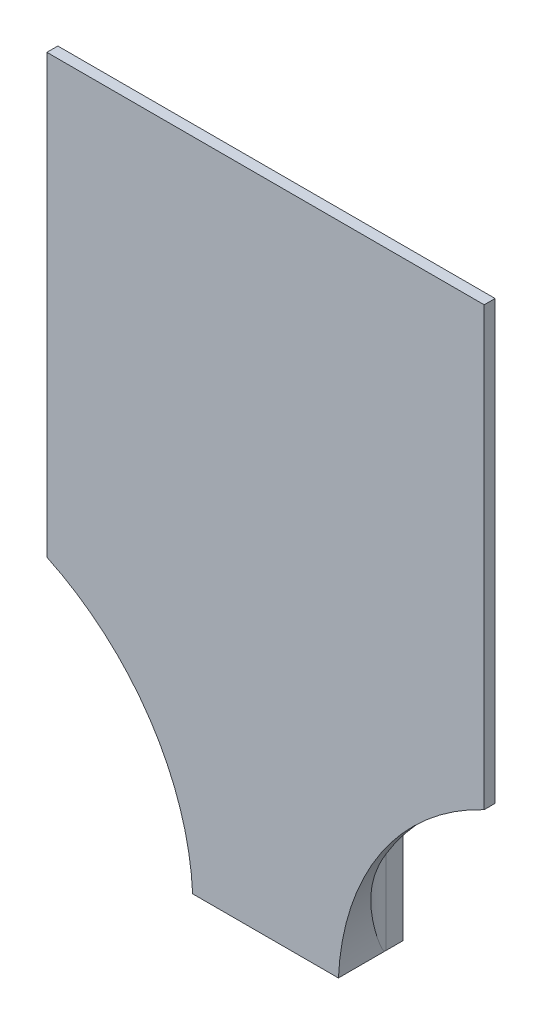
SolidWorks part; units mm, degrees
ref_plane "Płaszczyzna przednia" through (0, 0, 0) normal (0, 0, 1) x (1, 0, 0)
ref_plane "Płaszczyzna górna" through (0, 0, 0) normal (0, 1, 0) x (1, 0, 0)
ref_plane "Płaszczyzna prawa" through (0, 0, 0) normal (1, 0, 0) x (0, 0, -1)
sketch "Szkic1" plane through (0, 0, 0) normal (0, 1, 0) x (1, 0, 0)
  line L1 (-20, 10) -> (20, 10)
  line L2 (-20, 10) -> (-20, -10)
  line L3 (-20, -10) -> (20, -10)
  line L4 (20, 10) -> (20, -10)
  line L5 (-20, 10) -> (20, -10) construction
  line L6 (-20, -10) -> (20, 10) construction
  point P0 (0, 0)
  dimension "D1" = 40
  dimension "D2" = 20
extrude "Dodanie-wyciągnięcie1" add sketch "Szkic1" along normal blind 60
sketch "Szkic2" plane through (0, 60, 0) normal (0, 1, 0) x (1, 0, 0)
  line L0 (0, -10) -> (60, -10)
  line L1 (-20, -10) -> (20, -10) construction
  line L2 (60, -10) -> (60, -7)
  line L3 (60, -7) -> (-60, -7)
  line L4 (-60, -7) -> (-60, -10)
  line L5 (-60, -10) -> (0, -10)
  dimension "D1" = 60
  dimension "D2" = 60
  dimension "D3" = 3
extrude "Dodanie-wyciągnięcie2" add sketch "Szkic2" along normal blind 120
sketch "Szkic3" plane through (0, 0, 10) normal (0, 0, 1) x (1, 0, 0)
  line L0 (-60, 60) -> (-20, 60)
  line L1 (-20, 60) -> (-20, 0)
  line L4 (60, 60) -> (20, 60)
  line L5 (20, 60) -> (20, 0)
  arc A0 (20, 0) -> (60, 60) centre (89.923, -3.282) cw
  arc A1 (-60, 60) -> (-20, 0) centre (-89.923, -3.282) cw
  dimension "D1" = 70
  dimension "D2" = 70
extrude "Dodanie-wyciągnięcie3" add sketch "Szkic3" against normal blind 3
sketch "Szkic4" plane through (0, 60, 0) normal (0, 1, 0) x (1, 0, 0)
  line L8 (-20, -7) -> (20, -7)
  line L9 (20, -7) -> (20, 10)
  line L10 (20, 10) -> (-20, 10)
  line L11 (-20, 10) -> (-20, -7)
  line L12 (-20, -7) -> (20, -7)
  line L13 (20, -7) -> (20, 10)
  line L14 (20, 10) -> (-20, 10)
  line L15 (-20, 10) -> (-20, -7)
  dimension "D1" = 0
extrude "Dodanie-wyciągnięcie4" add sketch "Szkic4" along normal up to surface (120 mm away) up to face at (0, 180, 8.5)
sketch "Szkic5" plane through (20, 0, 0) normal (1, 0, 0) x (0, 0, -1)
  line L0 (-7, 180) -> (10, 10)
  line L1 (10, 180) -> (10, 0) construction
  line L2 (10, 10) -> (18.1242, 10)
  line L3 (18.1242, 10) -> (18.1242, 180)
  line L4 (18.1242, 180) -> (-7, 180)
  line L5 (-7, 0) -> (10, 0) construction
  dimension "D1" = 10
extrude "Wytnij-wyciągnięcie1" cut sketch "Szkic5" against normal up to surface (40 mm away) up to face at (-20, 90, -1.5)
sketch "Szkic6" plane through (0, 0, -10) normal (0, 0, -1) x (-1, 0, 0)
  line L0 (-20, 180) -> (-20, 0) construction
  line L1 (-17, 180) -> (17, 180)
  line L2 (-17, 180) -> (-17, 10)
  line L3 (-17, 10) -> (17, 10)
  line L4 (17, 180) -> (17, 10)
  line L5 (20, 0) -> (20, 180) construction
  line L6 (20, 180) -> (-20, 180) construction
  line L7 (20, 10) -> (-20, 10) construction
  dimension "D1" = 3
  dimension "D2" = 3
  dimension "D3" = 0
  dimension "D4" = 0
extrude "Wytnij-wyciągnięcie2" cut sketch "Szkic6" against normal up to surface (17 mm away) up to face at (37.9199, 106.3868, 7)
fillet "Zaokrąglenie1" radius 10 4 edges at (17, 95, 7) (20, 90, 7) (-17, 95, 7) (-20, 90, 7)
sketch "Szkic7" plane through (0, 0, 0) normal (0, -1, 0) x (1, 0, 0)
  line L0 (-33.7493, 0) -> (31.117, 0) construction
  circle A0 centre (-10, 0) radius 2
  circle A1 centre (10, 0) radius 2
  dimension "D1" = 4
  dimension "D2" = 4
  dimension "D3" = 10
  dimension "D4" = 10
extrude "Wytnij-wyciągnięcie3" cut sketch "Szkic7" against normal up to surface (10 mm away) up to face at (0, 10, -1.3096)
sketch "Szkic8" plane through (0, 0, 0) normal (0, -1, 0) x (1, 0, 0)
  circle A0 centre (-10, 0) radius 5.5
  circle A1 centre (10, 0) radius 5.5
  dimension "D1" = 11
  dimension "D2" = 11
extrude "Wytnij-wyciągnięcie4" cut sketch "Szkic8" against normal blind 6
fillet "Zaokrąglenie2" radius 2 4 edges at (10, 0, -5.5) (10, 6, -5.5) (-10, 0, -5.5) (-10, 6, -5.5)
sketch "Szkic9" plane through (0, 0, 0) normal (0, -1, 0) x (1, 0, 0)
  line L0 (20, -10) -> (-20, -10) construction
  line L1 (7.5, -10) -> (-7.5, -10)
  line L2 (-32.2487, 0.2513) -> (-32.2487, -13.0232)
  line L3 (-32.2487, -13.0232) -> (32.2487, -13.0232)
  line L4 (32.2487, -13.0232) -> (32.2487, 0.2513)
  arc A0 (32.2487, 0.2513) -> (7.5, -10) centre (7.5, 25) cw
  arc A1 (7.5, -10) -> (42.5, 25) centre (7.5, 25) ccw construction
  arc A2 (-7.5, -10) -> (-32.2487, 0.2513) centre (-7.5, 25) cw
  arc A3 (-42.5, 25) -> (-7.5, -10) centre (-7.5, 25) ccw construction
extrude "Wytnij-wyciągnięcie5" cut sketch "Szkic9" against normal through all
